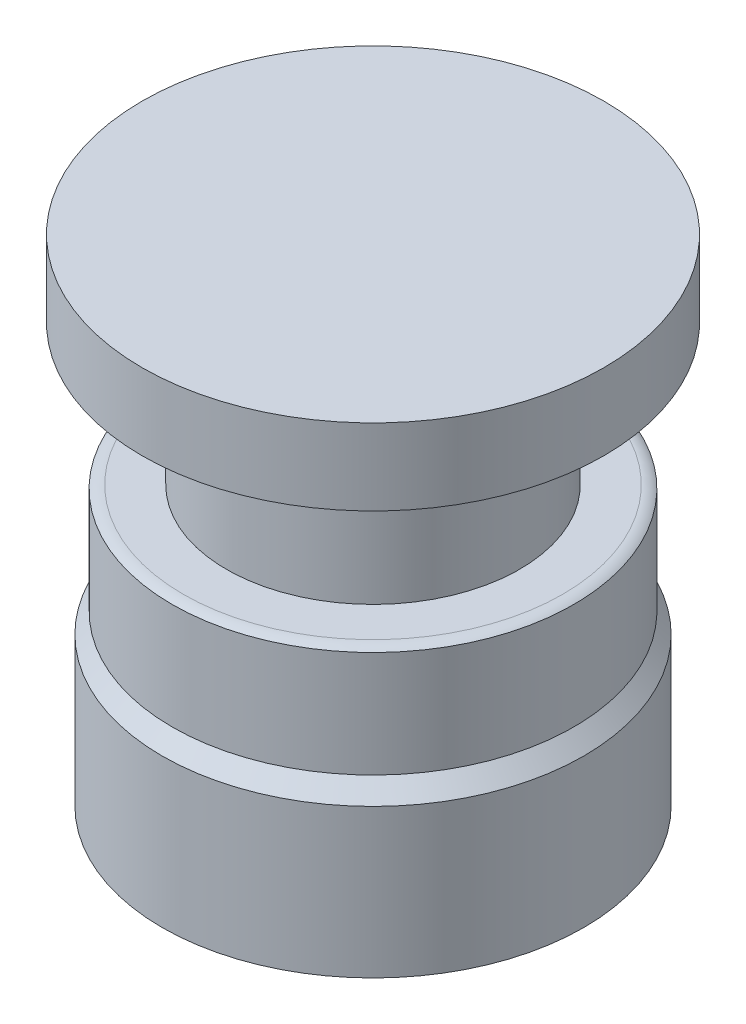
SolidWorks part; units mm, degrees
ref_plane "Front Plane" through (0, 0, 0) normal (0, 0, 1) x (1, 0, 0)
ref_plane "Top Plane" through (0, 0, 0) normal (0, 1, 0) x (1, 0, 0)
ref_plane "Right Plane" through (0, 0, 0) normal (1, 0, 0) x (0, 0, -1)
ref_axis "Axis_X" through (-88.99, 0, 0) along (1, 0, 0)
ref_axis "Axis_Y" through (0, 55, 0) along (0, -1, 0)
ref_axis "Axis_Z" through (0, 0, -88.99) along (0, 0, 1)
sketch "Sketch1" plane through (0, 0, 0) normal (0, 0, 1) x (1, 0, 0)
  line L0 (0, 0) -> (0, 24.65) construction
  line L1 (0, 0) -> (-10.5, 0)
  line L2 (-10.5, 0) -> (-10.5, 7.4)
  line L3 (-10.5, 7.4) -> (-9.5, 8.4)
  line L4 (-9.5, 8.4) -> (-10, 8.4)
  line L5 (-10, 8.4) -> (-10, 13.6852)
  line L6 (-9.45, 13.85) -> (-7.3, 13.85)
  line L7 (-7.3, 13.85) -> (-7.3, 20.85)
  line L8 (-7.3, 20.85) -> (-11.5, 20.85)
  line L9 (-11.5, 20.85) -> (-11.5, 24.65)
  line L10 (-11.5, 24.65) -> (0, 24.65)
  line L11 (0, 24.65) -> (0, 0)
  arc A0 (-9.45, 13.85) -> (-10, 13.6852) centre (-9.45, 12.85) ccw
  dimension "FIX_4" = 2
  dimension "FIX_9" = 21
  dimension "FIX_1" = 8.4
  dimension "FIX_2" = 1
  dimension "FIX_3" = 1
  dimension "FIX_10" = 20
  dimension "FIX_5" = 5.45
  dimension "FIX_6" = 0.55
  dimension "FIX_11" = 14.6
  dimension "FIX_12" = 23
  dimension "FIX_7" = 3.8
  dimension "FIX_8" = 24.65
revolve "Revolve1" add sketch "Sketch1" angle 360 about L0
equation "\"Factor\"= 1.082532"
